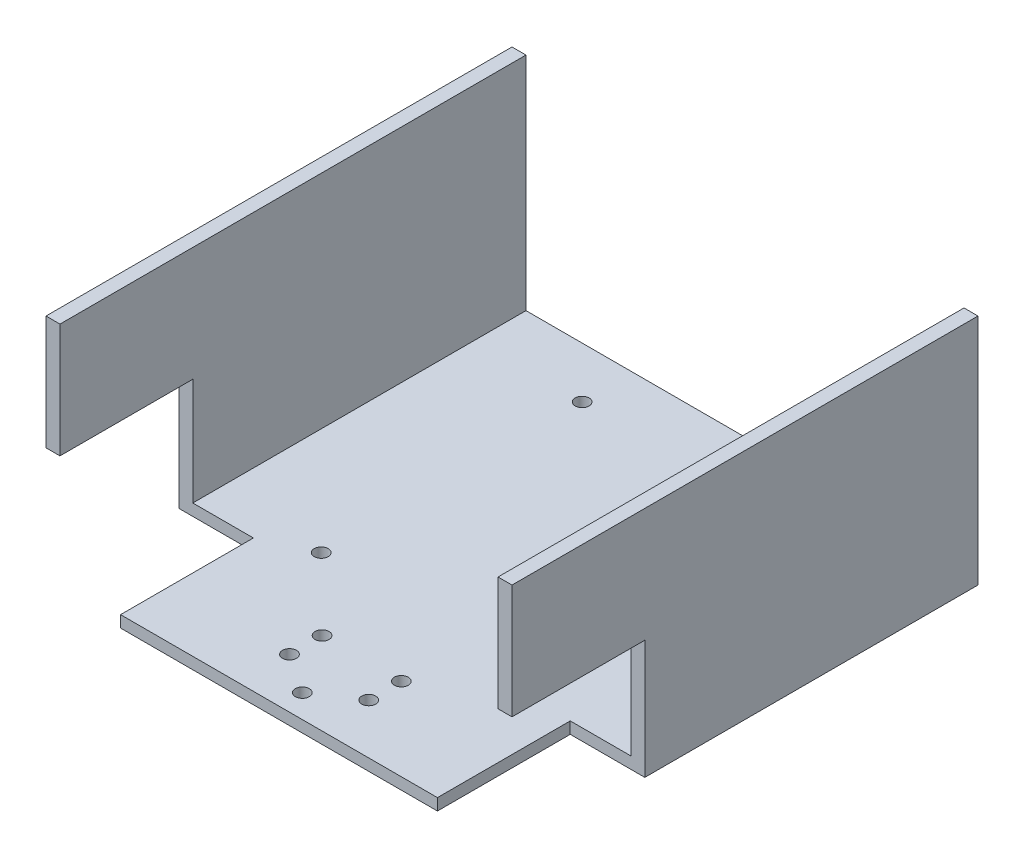
SolidWorks part; units mm, degrees
ref_plane "Alzado" through (0, 0, 0) normal (0, 0, 1) x (1, 0, 0)
ref_plane "Planta" through (0, 0, 0) normal (0, 1, 0) x (1, 0, 0)
ref_plane "Vista lateral" through (0, 0, 0) normal (1, 0, 0) x (0, 0, -1)
sketch "Croquis1" plane through (0, 0, 0) normal (0, 0, 1) x (1, 0, 0)
  line L0 (50, 0) -> (-50, 0)
  line L1 (-50, 0) -> (-50, 50)
  line L2 (-50, 50) -> (-47, 50)
  line L3 (-47, 50) -> (-47, 2.5)
  line L4 (-47, 2.5) -> (47, 2.5)
  line L5 (0, 2.5) -> (0, 0)
  line L6 (0, 0) -> (0, 13.9963) construction
  line L7 (47, 50) -> (47, 2.5)
  line L8 (50, 50) -> (47, 50)
  line L9 (50, 0) -> (50, 50)
  dimension "D1" = 50
  dimension "D2" = 50
  dimension "D3" = 3
  dimension "D4" = 2.5
extrude "Saliente-Extruir1" add sketch "Croquis1" against normal blind 100 contours L4 L7 L8 L9 L0 L1 L2 L3
sketch "Croquis2" plane through (0, 2.5, 0) normal (0, 1, 0) x (1, 0, 0)
  line L0 (0, 0) -> (0, 100) construction
  line L1 (-47, 0) -> (-34, 0)
  line L2 (-47, 0) -> (-47, 28.5)
  line L3 (-47, 28.5) -> (-34, 28.5)
  line L4 (-34, 0) -> (-34, 28.5)
  line L5 (-47, 100) -> (47, 100) construction
  line L6 (47, 28.5) -> (34, 28.5)
  line L7 (34, 0) -> (34, 28.5)
  line L8 (47, 0) -> (34, 0)
  line L9 (47, 0) -> (47, 28.5)
  dimension "D1" = 13
  dimension "D2" = 28.5
extrude "Cortar-Extruir2" cut sketch "Croquis2" against normal blind 10
ref_plane "Plano1" through (0, 2.5, 0) normal (0, 1, 0) x (1, 0, 0)
sketch "Croquis3" plane through (0, 2.5, 0) normal (0, 1, 0) x (1, 0, 0)
  line L0 (0, 0) -> (0, 100) construction
  line L1 (-47, 100) -> (47, 100) construction
  line L2 (-34, 0) -> (34, 0) construction
  circle A1 centre (0, 5) radius 1.5
  dimension "D1" = 3
  dimension "D2" = 5
extrude "Cortar-Extruir3" cut sketch "Croquis3" against normal blind 5
sketch "Croquis4" plane through (0, 2.5, 0) normal (0, 1, 0) x (1, 0, 0)
  line L0 (0, 0) -> (0, 100) construction
  line L1 (-47, 100) -> (47, 100) construction
  line L2 (0, 17.75) -> (-8.5, 17.75) construction
  line L3 (0, 10.75) -> (-8.5, 10.75) construction
  line L4 (-34, 14.25) -> (0, 14.25) construction
  line L6 (-34, 0) -> (-34, 28.5) construction
  circle A0 centre (-8.5, 17.75) radius 1.5
  circle A1 centre (-8.5, 10.75) radius 1.5
  circle A2 centre (8.5, 10.75) radius 1.5
  circle A3 centre (8.5, 17.75) radius 1.5
  dimension "D3" = 3
  dimension "D1" = 8.5
  dimension "D2" = 3.5
  dimension "D4" = 3.5
extrude "Cortar-Extruir4" cut sketch "Croquis4" against normal blind 10
sketch "Croquis5" plane through (0, 2.5, 0) normal (0, 1, 0) x (1, 0, 0)
  line L0 (-24, 100) -> (-24, 89.05) construction
  line L1 (-47, 100) -> (47, 100) construction
  line L2 (-47, 100) -> (-47, 0) construction
  line L3 (0, 100) -> (0, 0) construction
  circle A0 centre (-24, 89.05) radius 1.5
  circle A1 centre (-24, 33.05) radius 1.5
  circle A2 centre (24, 33.05) radius 1.5
  circle A3 centre (24, 89.05) radius 1.5
  dimension "D3" = 3
  dimension "D1" = 10.95
  dimension "D2" = 23
  dimension "D4" = 56
extrude "Cortar-Extruir6" cut sketch "Croquis5" against normal blind 10
sketch "Croquis6" plane through (-50, 0, 0) normal (-1, 0, 0) x (0, 0, 1)
  line L1 (0, 25.5) -> (0, 2.5)
  line L4 (-100, 0) -> (0, 0) construction
  line L6 (0, 2.5) -> (-28.5, 2.5)
  line L7 (0, 0) -> (0, 50) construction
  line L8 (-28.5, 2.5) -> (-28.5, 25.5)
  line L9 (-28.5, 25.5) -> (0, 25.5)
  dimension "D1" = 28.5
  dimension "D2" = 23
  dimension "D3" = 2.5
extrude "Cortar-Extruir8" cut sketch "Croquis6" against normal through all
sketch "Croquis7" plane through (0, 0, 0) normal (0, 0, 1) x (1, 0, 0)
  line L4 (-47, 2.5) -> (-50, 2.5)
  line L5 (-50, 2.5) -> (-50, 0)
  line L6 (-50, 0) -> (-47, 0)
  line L7 (-47, 0) -> (-47, 2.5)
  line L8 (-47, 2.5) -> (-50, 2.5)
  line L9 (-50, 2.5) -> (-50, 0)
  line L10 (-50, 0) -> (-47, 0)
  line L11 (-47, 0) -> (-47, 2.5)
  line L12 (50, 2.5) -> (47, 2.5)
  line L13 (47, 2.5) -> (47, 0)
  line L14 (47, 0) -> (50, 0)
  line L15 (50, 0) -> (50, 2.5)
  line L16 (50, 2.5) -> (47, 2.5)
  line L17 (47, 2.5) -> (47, 0)
  line L18 (47, 0) -> (50, 0)
  line L19 (50, 0) -> (50, 2.5)
  dimension "D1" = 0
  dimension "D2" = 0
extrude "Cortar-Extruir9" cut sketch "Croquis7" against normal blind 28.5
